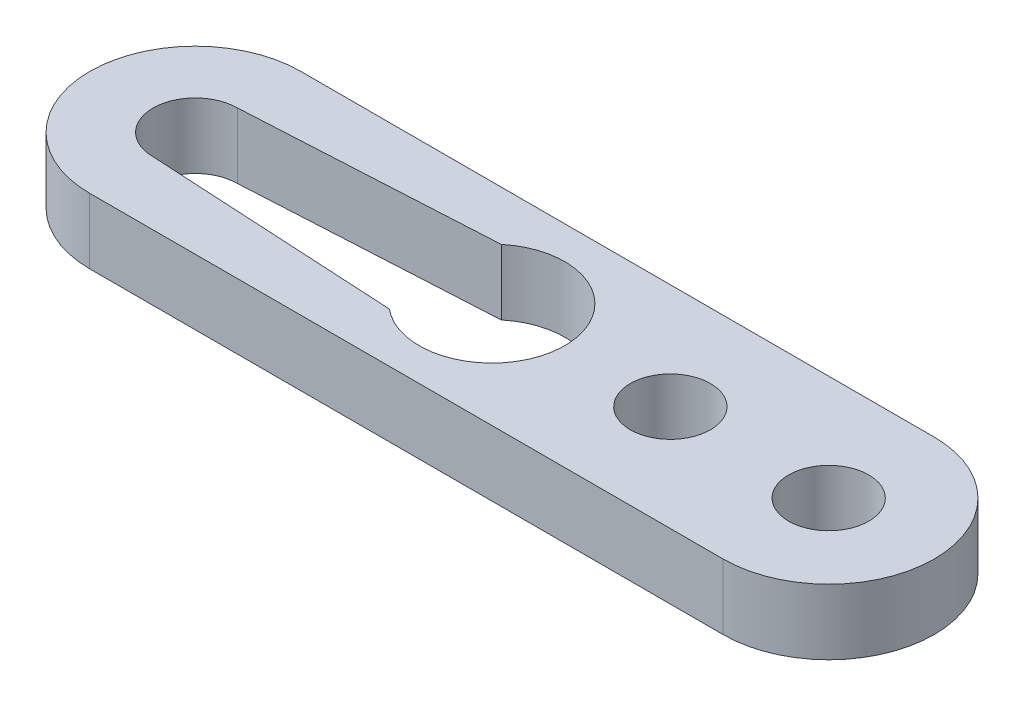
SolidWorks part; units mm, degrees
ref_plane "Front Plane" through (0, 0, 0) normal (0, 0, 1) x (1, 0, 0)
ref_plane "Top Plane" through (0, 0, 0) normal (0, 1, 0) x (1, 0, 0)
ref_plane "Right Plane" through (0, 0, 0) normal (1, 0, 0) x (0, 0, -1)
sketch "Sketch1" plane through (0, 0, 0) normal (0, 1, 0) x (1, 0, 0)
  line L0 (-15, 0) -> (15, 0) construction
  line L1 (-15, 5) -> (15, 5)
  line L2 (-15, -5) -> (15, -5)
  line L3 (-0.95, 0) -> (-3.1591, 2.65) construction
  line L4 (-0.95, 0) -> (-3.1591, -2.65) construction
  line L5 (-3.1591, 2.65) -> (-3.1591, -2.65) construction
  line L6 (-15, 2) -> (-3.1591, 2.65)
  line L7 (-15, -2) -> (-3.1591, -2.65)
  arc A0 (-15, 5) -> (-15, -5) centre (-15, 0) ccw
  arc A1 (15, -5) -> (15, 5) centre (15, 0) ccw
  arc A2 (-15, -2) -> (-15, 2) centre (-15, 0) cw
  arc A3 (-3.1591, -2.65) -> (-3.1591, 2.65) centre (-0.95, 0) ccw
  point P3 (0, 0)
  dimension "D2" = 5
  dimension "D3" = 2
  dimension "D4" = 3.45
  dimension "D5" = 14.05
  dimension "D1" = 30
  dimension "D6" = 100.37
  dimension "D7" = 11.8409
extrude "Boss-Extrude1" add sketch "Sketch1" along normal blind 3 and the other way blind 0.1
hole_wizard "#6 Clearance Hole1" positions "Sketch2" profile "Sketch3" hole size "#6" standard "ANSI Inch" end condition through all
sketch "Sketch2" plane through (0, 3, 0) normal (0, 1, 0) x (1, 0, 0)
  point P0 (7.5, 0)
  point P2 (15, 0)
  dimension "D1" = 7.5
  dimension "D2" = 15
sketch "Sketch3" plane through (7.5, 3, 0) normal (1, 0, 0) x (0, 0, 1)
  line L0 (0, 0) -> (0, 3.1)
  line L1 (0, 3.1) -> (1.8986, 3.1)
  line L2 (1.8986, 3.1) -> (1.8986, 0)
  line L5 (1.8986, 0) -> (0, 0)
  line L11 (0, -6.35) -> (0, 107.95) construction
  dimension "Thru Hole Dia." = 3.7973
  dimension "Thru Hole Depth" = 3.1
equation "\"D2@Sketch2\"=\"D1@Sketch2\"*2"
